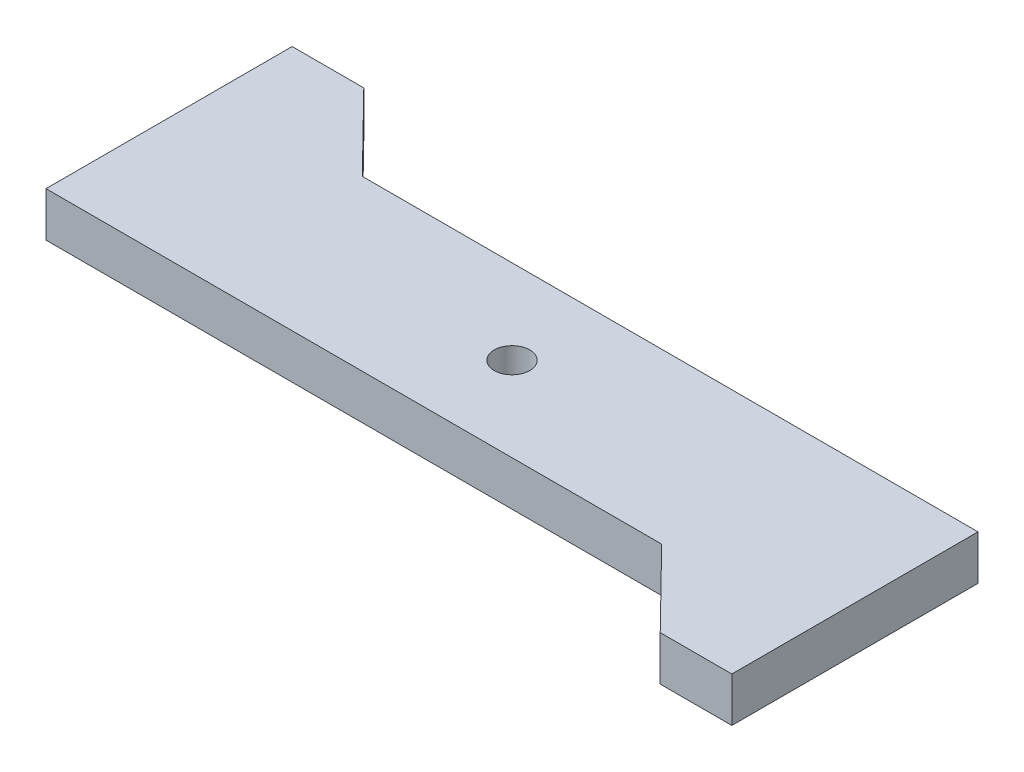
SolidWorks part; units mm, degrees
ref_plane "Front Plane" through (0, 0, 0) normal (0, 0, 1) x (1, 0, 0)
ref_plane "Top Plane" through (0, 0, 0) normal (0, 1, 0) x (1, 0, 0)
ref_plane "Right Plane" through (0, 0, 0) normal (1, 0, 0) x (0, 0, -1)
sketch "Sketch1" plane through (0, 0, 0) normal (0, 1, 0) x (1, 0, 0)
  line L0 (-85, -37.5) -> (85, 37.5) construction
  line L1 (-85.5361, 0) -> (85.5361, 0) construction
  line L2 (-85.5361, 18.9153) -> (-85.5361, -18.9153)
  line L3 (85.5361, 18.9153) -> (85.5361, -18.9153)
  line L4 (-52.4639, 18.9153) -> (85.5361, 18.9153)
  line L5 (-85.5361, -18.9153) -> (52.4639, -18.9153)
  line L6 (-85.5361, 18.9153) -> (-85.5361, 36.2605)
  line L7 (-85.5361, 36.2605) -> (-69.484, 36.2605)
  line L8 (-69.484, 36.2605) -> (-52.4639, 18.9153)
  line L9 (85.5361, -18.9153) -> (85.5361, -36.2605)
  line L10 (85.5361, -36.2605) -> (69.484, -36.2605)
  line L11 (69.484, -36.2605) -> (52.4639, -18.9153)
  point P2 (0, 0)
  point P10 (-85.5361, 0)
  point P11 (85.5361, 0)
  point P14 (0, 0)
  dimension "D1" = 75
  dimension "D2" = 170
extrude "Boss-Extrude1" add sketch "Sketch1" along normal blind 10
sketch "Sketch2" plane through (0, 10, 0) normal (0, 1, 0) x (1, 0, 0)
  circle A0 centre (0, 0) radius 4
extrude "Cut-Extrude1" cut sketch "Sketch2" against normal blind 20
